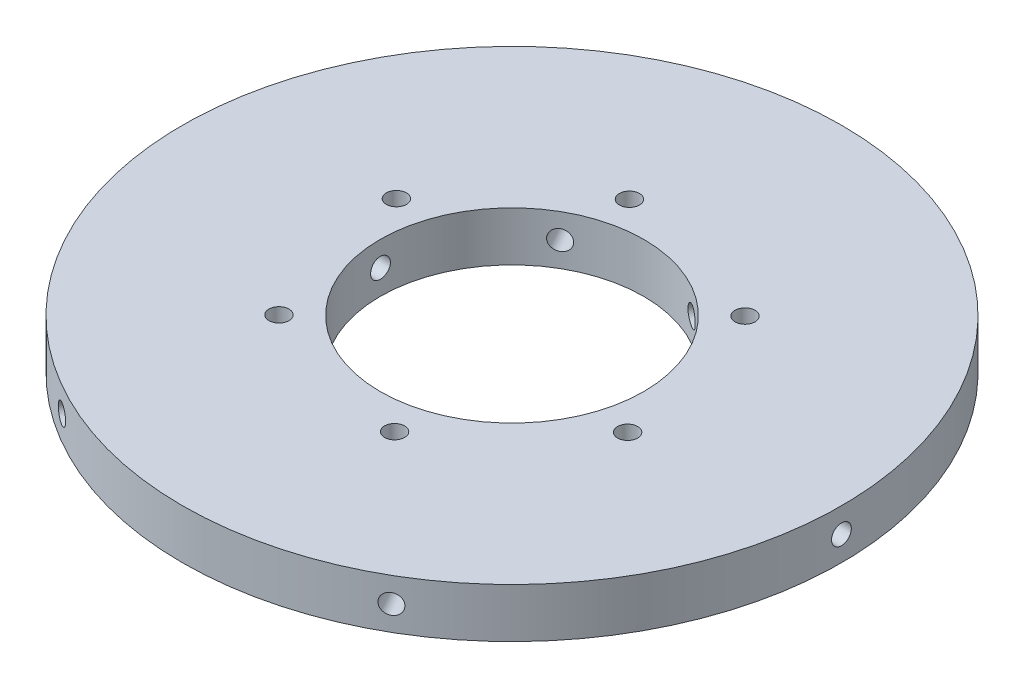
SolidWorks part; units mm, degrees
ref_plane "Front Plane" through (0, 0, 0) normal (0, 0, 1) x (1, 0, 0)
ref_plane "Top Plane" through (0, 0, 0) normal (0, 1, 0) x (1, 0, 0)
ref_plane "Right Plane" through (0, 0, 0) normal (1, 0, 0) x (0, 0, -1)
sketch "Sketch1" plane through (0, 0, 0) normal (0, 1, 0) x (1, 0, 0)
  line L0 (0, 0) -> (0, 87.698) construction
  line L1 (0, 0) -> (-128.1213, 0) construction
  circle A0 centre (0, 0) radius 100
  circle A1 centre (0, 0) radius 40
  circle A2 centre (12.723, -48.3542) radius 3.05
  dimension "D1" = 200
  dimension "D2" = 80
extrude "Boss-Extrude1" add sketch "Sketch1" along normal blind 15
sketch "Sketch2" plane through (0, 0, 0) normal (1, 0, 0) x (0, 0, -1)
  line L0 (100, 7.5) -> (-100, 7.5) construction
  line L1 (100, 0) -> (100, 15) construction
  line L2 (-100, 15) -> (-100, 0) construction
  circle A0 centre (0, 7.5) radius 3
  dimension "D1" = 6
extrude "Cut-Extrude1" cut sketch "Sketch2" against normal through all
pattern_circular "CirPattern1" count 6 over 360 about axis through (0, 15, 0) along (0, 1, 0) of "Cut-Extrude1"
pattern_circular "CirPattern2" count 6 every 60 about axis through (0, 15, 0) along (0, 1, 0) of face at (12.723, 15, 51.4042)
equation "\"holes\"=6"
equation "\"D1@CirPattern1\"=\"holes\""
